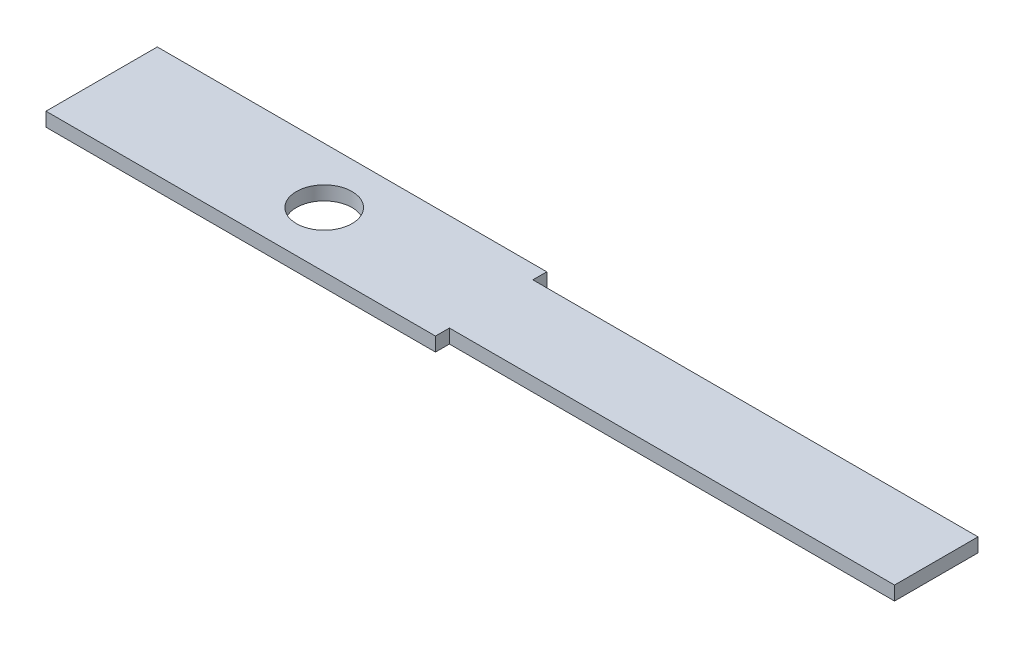
SolidWorks part; units mm, degrees
ref_plane "Front Plane" through (0, 0, 0) normal (0, 0, 1) x (1, 0, 0)
ref_plane "Top Plane" through (0, 0, 0) normal (0, 1, 0) x (1, 0, 0)
ref_plane "Right Plane" through (0, 0, 0) normal (1, 0, 0) x (0, 0, -1)
sketch "Sketch1" plane through (0, 0, 0) normal (0, 1, 0) x (1, 0, 0)
  line L0 (0, 6.35) -> (-31.75, 6.35) construction
  line L1 (0, 0) -> (-31.75, 0)
  line L2 (0, 0) -> (0, 12.7)
  line L3 (0, 12.7) -> (-31.75, 12.7)
  line L4 (-31.75, 0) -> (-31.75, 12.7)
  line L5 (0, 12.7) -> (12.7, 12.7)
  line L6 (12.7, 12.7) -> (12.7, 11.1125)
  line L7 (12.7, 11.1125) -> (63.5, 11.1125)
  line L8 (63.5, 11.1125) -> (63.5, 1.5875)
  line L9 (63.5, 1.5875) -> (12.7, 1.5875)
  line L10 (12.7, 1.5875) -> (12.7, 0)
  line L11 (12.7, 0) -> (0, 0)
  circle A0 centre (-6.35, 6.35) radius 3.175
  dimension "D4" = 6.35
  dimension "D1" = 12.7
  dimension "D2" = 31.75
  dimension "D3" = 6.35
  dimension "D5" = 12.7
  dimension "D6" = 50.8
  dimension "D7" = 9.525
extrude "Boss-Extrude1" add sketch "Sketch1" along normal blind 1.5875 contours L2 L0 A0 L4 L1 | L0 L2 L3 L4 A0 | L11 L10 L9 L8 L7 L6 L5 L2 region at (-16.6869, 0, -3.0192) region at (30.1625, 0, -6.35) region at (-16.6869, 0, -9.6808)
